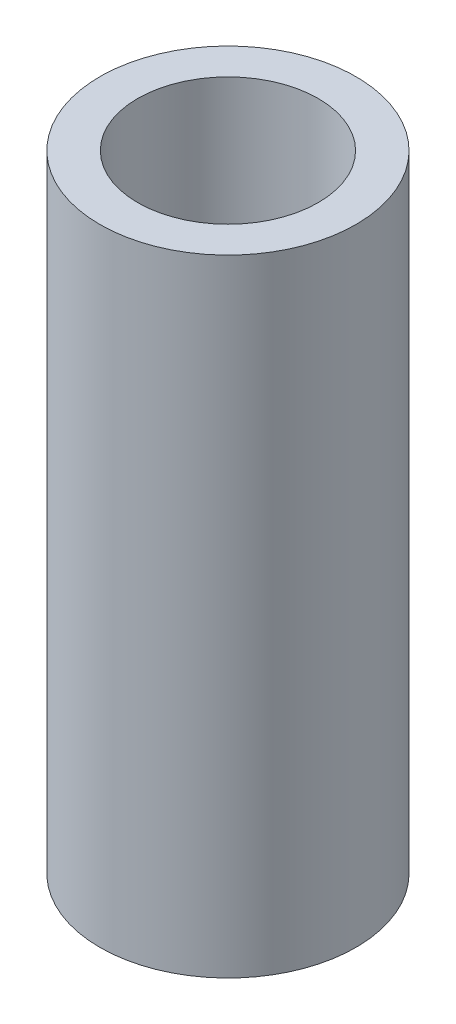
SolidWorks part; units mm, degrees
ref_plane "Front Plane" through (0, 0, 0) normal (0, 0, 1) x (1, 0, 0)
ref_plane "Top Plane" through (0, 0, 0) normal (0, 1, 0) x (1, 0, 0)
ref_plane "Right Plane" through (0, 0, 0) normal (1, 0, 0) x (0, 0, -1)
sketch "Sketch1" plane through (0, 0, 0) normal (0, 1, 0) x (1, 0, 0)
  circle A0 centre (0, 0) radius 35
  dimension "SLEEVE_OD" = 70
extrude "Boss-Extrude1" add sketch "Sketch1" along normal blind 171.1028
sketch "Sketch2" plane through (0, 0, 0) normal (0, 1, 0) x (1, 0, 0)
  circle A0 centre (0, 0) radius 24.6686
  dimension "BORE_D" = 49.3373
extrude "Cut-Extrude1" cut sketch "Sketch2" along normal through all
chamfer "Chamfer1" distance 3.9222 angle 60 rebuild error yes
